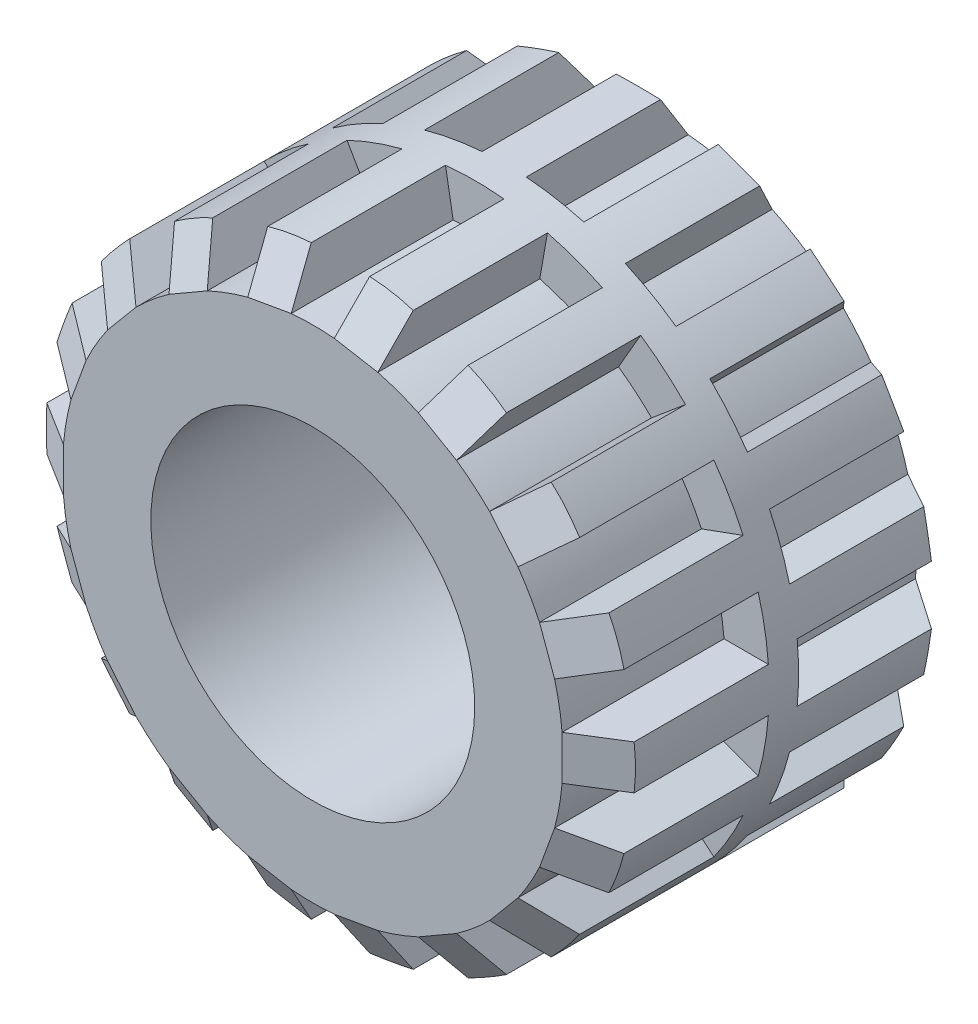
SolidWorks part; units mm, degrees
ref_plane "Front Plane" through (0, 0, 0) normal (0, 0, 1) x (1, 0, 0)
ref_plane "Top Plane" through (0, 0, 0) normal (0, 1, 0) x (1, 0, 0)
ref_plane "Right Plane" through (0, 0, 0) normal (1, 0, 0) x (0, 0, -1)
sketch "Sketch1" plane through (0, 0, 0) normal (0, 0, 1) x (1, 0, 0)
  circle A0 centre (0, 0) radius 8.5
  circle A1 centre (0, 0) radius 5.5
  dimension "D1" = 17
  dimension "D2" = 3
extrude "Boss-Extrude1" add sketch "Sketch1" along normal mid plane 12
sketch "Sketch3" plane through (0, 0, 0) normal (0, 0, 1) x (1, 0, 0)
  circle A0 centre (0, 0) radius 10
  circle A1 centre (0, 0) radius 8.5 construction
  circle A3 centre (0, 0) radius 8.5
  dimension "D1" = 1.5
extrude "Boss-Extrude3" add sketch "Sketch3" along normal mid plane 1
sketch "Sketch4" plane through (0, 0, -0.5) normal (0, 0, -1) x (-1, 0, 0)
  line L0 (-0.75, 8.4668) -> (-0.75, 9.9718)
  line L1 (0.75, 8.4668) -> (0.75, 9.9718)
  line L2 (0, 13.0864) -> (0, -11.9753) construction
  circle A3 centre (0, 0) radius 8.5 construction
  circle A4 centre (0, 0) radius 10 construction
  circle A5 centre (0, 0) radius 8.5 construction
  arc A6 (-0.75, 9.9718) -> (0.75, 9.9718) centre (0, 0) cw
  arc A7 (-0.75, 8.4668) -> (0.75, 8.4668) centre (0, 0) cw
  dimension "D1" = 0.75
  dimension "D2" = 1.5
extrude "Boss-Extrude4" add sketch "Sketch4" along normal blind 5.5
sketch "Sketch5" plane through (-0.75, 0, 0) normal (-1, 0, 0) x (0, 0, 1)
  line L0 (-6, 8.4668) -> (-5, 10.0668)
  line L3 (-6, 10.0668) -> (-6, 8.4668)
  line L4 (-6, 10.0668) -> (-5, 10.0668)
  dimension "D1" = 1
  dimension "D2" = 1.6
extrude "Cut-Extrude1" cut sketch "Sketch5" against normal up to surface (1.5 mm away) up to face at (0.75, 9.2193, -3.25)
pattern_circular "CirPattern1" count 18 over 360 about axis through (0, 0, -6) along (0, 0, 1) of "Boss-Extrude4", "Cut-Extrude1" reverse direction yes
mirror "Mirror1" about plane through (0, 0, 0) normal (0, 0, 1) of "CirPattern1", "Boss-Extrude4"
split "Split1" trim tools "Front Plane" bodies to split 106 resulting bodies 107 108
move or copy body "Body-Move/Copy1" bodies to move or copy 107 copy no rotation origin (0, 0, 0) rotation axis (0, 0, 1) rotation angle 10
combine bodies "Combine1" operation type add bodies to combine 108 109
